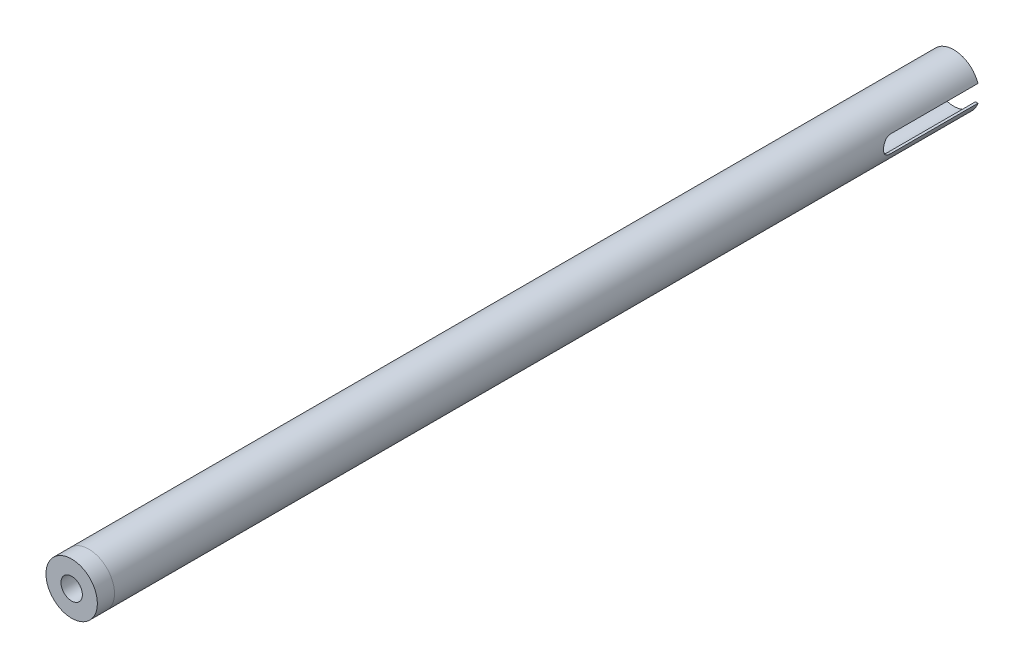
SolidWorks part; units mm, degrees
material "AISI 4130 Steel, normalized at 870C"
ref_plane "Front Plane" through (0, 0, 0) normal (0, 0, 1) x (1, 0, 0)
ref_plane "Top Plane" through (0, 0, 0) normal (0, 1, 0) x (1, 0, 0)
ref_plane "Right Plane" through (0, 0, 0) normal (1, 0, 0) x (0, 0, -1)
sketch "Axis" plane through (0, 0, 0) normal (0, 1, 0) x (1, 0, 0)
  line L0 (0, 0) -> (0, 326.9105) construction
  line L1 (0, 0) -> (0, -28.575) construction
  line L2 (0, 326.9105) -> (-9.525, 326.9105) construction
  line L4 (0, 361.4126) -> (-10.3188, 324.0353) construction
  dimension "D1" = 28.575
  dimension "D2" = 9.525
sketch "Sketch1" plane through (0, 0, 0) normal (0, 0, 1) x (1, 0, 0)
  line L0 (-9.525, 0) -> (9.525, 0) construction
  line L1 (-8.9803, 3.175) -> (8.9803, 3.175)
  line L2 (-8.9803, -3.175) -> (8.9803, -3.175)
  circle A0 centre (0, 0) radius 9.525
  circle A1 centre (0, 0) radius 8.636
  circle A2 centre (0, 0) radius 3.9688
  dimension "D1" = 19.05
  dimension "D3" = 7.9375
  dimension "D2" = 0.889
  dimension "D4" = 6.35
extrude "Threaded insert 1-1" add sketch "Sketch1" against normal blind 6.35 contours A2 L1 A1 | A1 L1 A0 | A2 L0 A1 L1 | A1 L0 A0 L1 | L0 A1 L2 A0 | L0 A2 L2 A1 | A2 L2 A1 | A1 L2 A0 | L0 A1 L2 A2 | L0 A0 L2 A1 | A0 L0 A1 L1 | A1 L0 A2 L1 region at (5.9465, 1.6355, 0) region at (5.9465, -1.6355, 0) region at (8.8881, 1.6046, 0) region at (8.8881, -1.6046, 0) region at (-5.9465, -1.6355, 0) region at (-5.9465, 1.6355, 0) region at (0, 5.5139, 0) region at (0, -5.5139, 0) region at (0, 8.8265, 0) region at (8.5057, -3.3655, 0) region at (-8.8881, -1.6046, 0) region at (-8.8881, 1.6046, 0)
extrude "Threaded insert 1-2" add sketch "Sketch1<3>" against normal blind 9.525 from surface contours A2 L1 A1 | A2 L0 A1 L1 | L0 A2 L2 A1 | A2 L2 A1 | L0 A1 L2 A2 | A1 L0 A2 L1 region at (5.9465, 1.6355, 0) region at (5.9465, -1.6355, 0) region at (-5.9465, -1.6355, 0) region at (-5.9465, 1.6355, 0) region at (0, 5.5139, 0) region at (0, -5.5139, 0) starting at face at (9.525, 0, -6.35)
sketch "Sketch1<3>" plane through (0, 0, 0) normal (0, 0, 1) x (1, 0, 0) same geometry as "Sketch1"
extrude "A-arm tube" add sketch "Sketch1<4>" against normal up to vertex (326.9105 mm away) from surface separate body contours A1 L1 A0 | A1 L0 A0 L1 | L0 A1 L2 A0 | A1 L2 A0 | L0 A0 L2 A1 | A0 L0 A1 L1 region at (8.8881, 1.6046, 0) region at (8.8881, -1.6046, 0) region at (0, 8.8265, 0) region at (8.5057, -3.3655, 0) region at (-8.8881, -1.6046, 0) region at (-8.8881, 1.6046, 0) up to point (0, 0, -326.9105) starting at face at (8.636, 0, -6.35)
sketch "Sketch1<4>" plane through (0, 0, 0) normal (0, 0, 1) x (1, 0, 0) same geometry as "Sketch1"
extrude "Apex slot" cut sketch "Sketch1<5>" along normal blind 35.56 from surface contours A0 L0 A1 L1 | L0 A0 L2 A1 | A1 L0 A0 L1 | L0 A1 L2 A0 region at (8.8881, 1.6046, 0) region at (8.8881, -1.6046, 0) region at (-8.8881, -1.6046, 0) region at (-8.8881, 1.6046, 0) starting at face at (8.636, 0, -326.9105)
sketch "Sketch1<5>" plane through (0, 0, 0) normal (0, 0, 1) x (1, 0, 0) same geometry as "Sketch1"
fillet "Fillet1" radius 3.175 4 edges at (-8.5057, 3.175, -291.3505) (-8.5057, -3.175, -291.3505) (8.5057, -3.175, -291.3505) (8.5057, 3.175, -291.3505)
equation "\"tube diameter\"= 3 / 4"
equation "\"tube thickness\"= .035"
equation "\"apex thickness\"= .25"
equation "\"tube slot\"= 1.4"
equation "\"D1@Sketch1\"=\"tube diameter\""
equation "\"D2@Sketch1\"=\"tube thickness\""
equation "\"threaded insert hole\"= .3125"
equation "\"D3@Sketch1\"=\"threaded insert hole\""
equation "\"D4@Sketch1\"=\"apex thickness\""
equation "\"D1@Apex slot\" = \"tube slot\""
equation "\"D1@Fillet1\"=\"apex thickness\"/2"
equation "\"D2@Axis\"=\"tube diameter\"/2"
